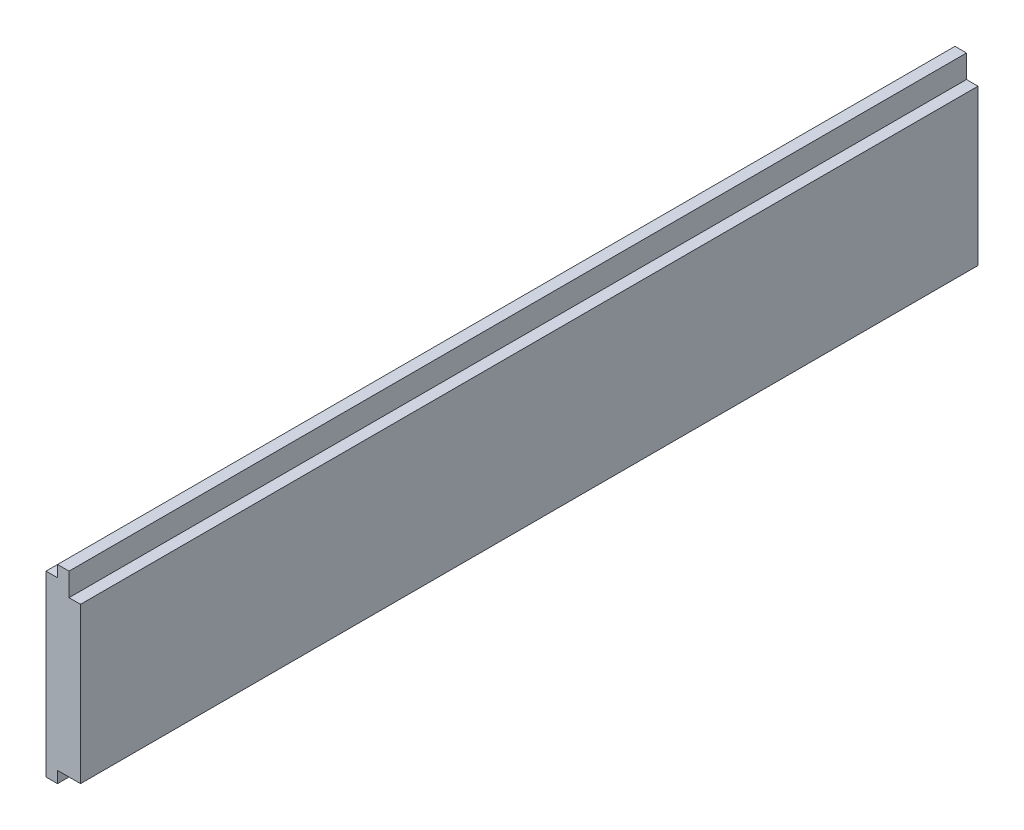
SolidWorks part; units mm, degrees
material "Сосна"
ref_plane "Спереди" through (0, 0, 0) normal (0, 0, 1) x (1, 0, 0)
ref_plane "Сверху" through (0, 0, 0) normal (0, 1, 0) x (1, 0, 0)
ref_plane "Справа" through (0, 0, 0) normal (1, 0, 0) x (0, 0, -1)
sketch "Эскиз1" plane through (0, 0, 0) normal (0, 0, 1) x (1, 0, 0)
  line L0 (0, 0) -> (0, 155)
  line L1 (0, 155) -> (10, 155)
  line L2 (10, 155) -> (10, 165)
  line L3 (10, 165) -> (20, 165)
  line L4 (20, 165) -> (20, 145)
  line L5 (20, 145) -> (30, 145)
  line L6 (30, 145) -> (30, 10)
  line L7 (30, 10) -> (10, 10)
  line L8 (10, 10) -> (10, 0)
  line L9 (10, 0) -> (0, 0)
  dimension "D1" = 10
  dimension "D2" = 10
  dimension "D3" = 10
  dimension "D4" = 10
  dimension "D5" = 20
  dimension "D6" = 10
  dimension "D7" = 10
  dimension "D8" = 155
extrude "Бобышка-Вытянуть1" add sketch "Эскиз1" along normal blind 780
